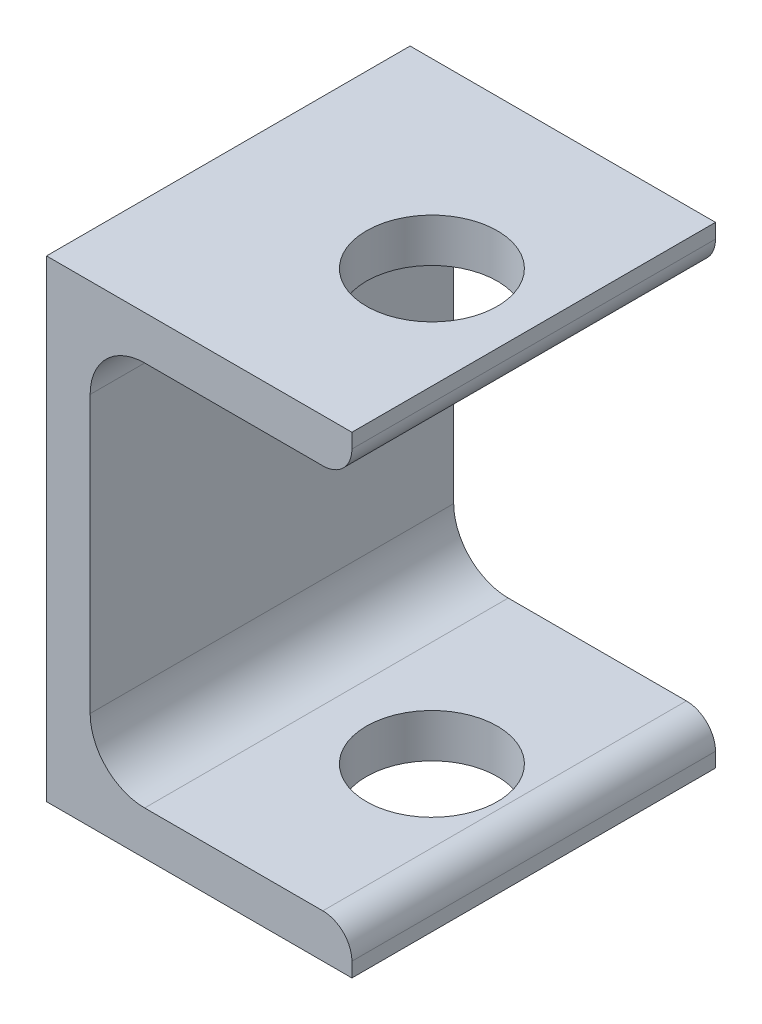
SolidWorks part; units mm, degrees
material "1.0037 (S235JR)"
ref_plane "Płaszczyzna przednia" through (0, 0, 0) normal (0, 0, 1) x (1, 0, 0)
ref_plane "Płaszczyzna górna" through (0, 0, 0) normal (0, 1, 0) x (1, 0, 0)
ref_plane "Płaszczyzna prawa" through (0, 0, 0) normal (1, 0, 0) x (0, 0, -1)
sketch "Szkic1" plane through (0, 0, 0) normal (0, 0, 1) x (1, 0, 0)
  line L0 (0, 0) -> (0, -65)
  line L1 (0, -65) -> (42, -65)
  line L2 (42, -65) -> (42, -63)
  line L3 (38, -59) -> (13.5, -59)
  line L4 (6, -51.5) -> (6, -13.5)
  line L5 (13.5, -6) -> (38, -6)
  line L6 (42, -2) -> (42, 0)
  line L7 (42, 0) -> (0, 0)
  arc A0 (13.5, -59) -> (6, -51.5) centre (13.5, -51.5) cw
  arc A1 (6, -13.5) -> (13.5, -6) centre (13.5, -13.5) cw
  arc A2 (42, -63) -> (38, -59) centre (38, -63) ccw
  arc A3 (38, -6) -> (42, -2) centre (38, -2) ccw
  dimension "D7" = 7.5
  dimension "D8" = 4
  dimension "D1" = 65
  dimension "D3" = 42
  dimension "D4" = 6
  dimension "D5" = 6
  dimension "D6" = 6
extrude "Dodanie-wyciągnięcie1" add sketch "Szkic1" along normal blind 50
sketch "Szkic2" plane through (0, 0, 0) normal (0, 1, 0) x (1, 0, 0)
  line L0 (0, -50) -> (0, 0) construction
  line L1 (42, 0) -> (0, 0) construction
  circle A0 centre (28, -25) radius 9
  dimension "D1" = 18
  dimension "D2" = 28
  dimension "D3" = 25
extrude "Wytnij-wyciągnięcie1" cut sketch "Szkic2" against normal up to surface (65 mm away) up to face at (21, -65, 25)
equation "\"D5@Szkic1\"=\"D4@Szkic1\""
equation "\"D6@Szkic1\"=\"D4@Szkic1\""
